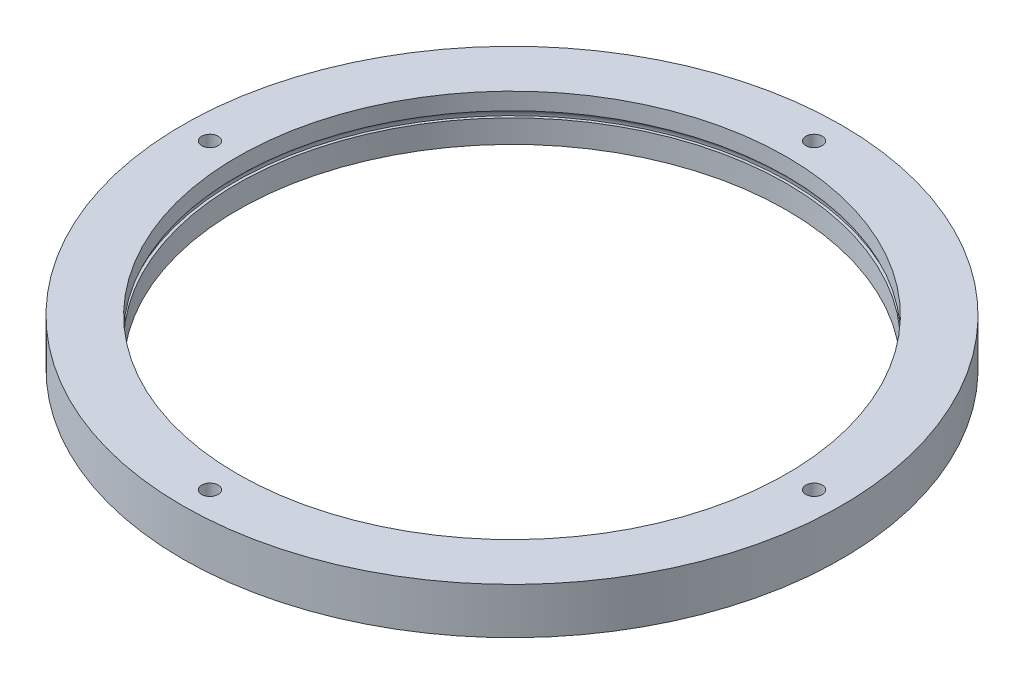
SolidWorks part; units mm, degrees
ref_plane "前视基准面" through (0, 0, 0) normal (0, 0, 1) x (1, 0, 0)
ref_plane "上视基准面" through (0, 0, 0) normal (0, 1, 0) x (1, 0, 0)
ref_plane "右视基准面" through (0, 0, 0) normal (1, 0, 0) x (0, 0, -1)
other "Configuration Table"
sketch "草图1" plane through (0, 0, 0) normal (0, 1, 0) x (1, 0, 0)
  circle A0 centre (0, 0) radius 60
  circle A1 centre (0, 0) radius 50
  dimension "D1" = 120
  dimension "D2" = 10
extrude "凸台-拉伸2" add sketch "草图1" along normal blind 8.4
sketch "草图4" plane through (0, 0, 0) normal (0, 0, 1) x (1, 0, 0)
  line L1 (-50.5, 4.1849) -> (0, 4.1849)
  line L4 (0, 5.303) -> (0, 3.0669)
  line L5 (-50, 5.303) -> (0, 5.303)
  line L6 (0, 5.303) -> (0, 3.0669)
  line L7 (0, 3.0669) -> (-50, 3.0669)
  arc A0 (-50.5, 4.1849) -> (-50, 5.303) centre (-49, 4.1849) cw
  arc A1 (-50.5, 4.1849) -> (-50, 3.0669) centre (-49, 4.1849) ccw
  point P5 (-50, 4.1849)
revolve "切除-旋转1" cut sketch "草图4" angle 360 about L4 region at (-25.1734, 4.7431, 0)
sketch "草图5" plane through (0, 8.4, 0) normal (0, 1, 0) x (1, 0, 0)
  circle A2 centre (0, 55) radius 1.5
  circle A3 centre (55, 0) radius 1.5
  circle A4 centre (-55, 0) radius 1.5
  circle A5 centre (0, -55) radius 1.5
extrude "切除-拉伸1" cut sketch "草图5" against normal blind 10
